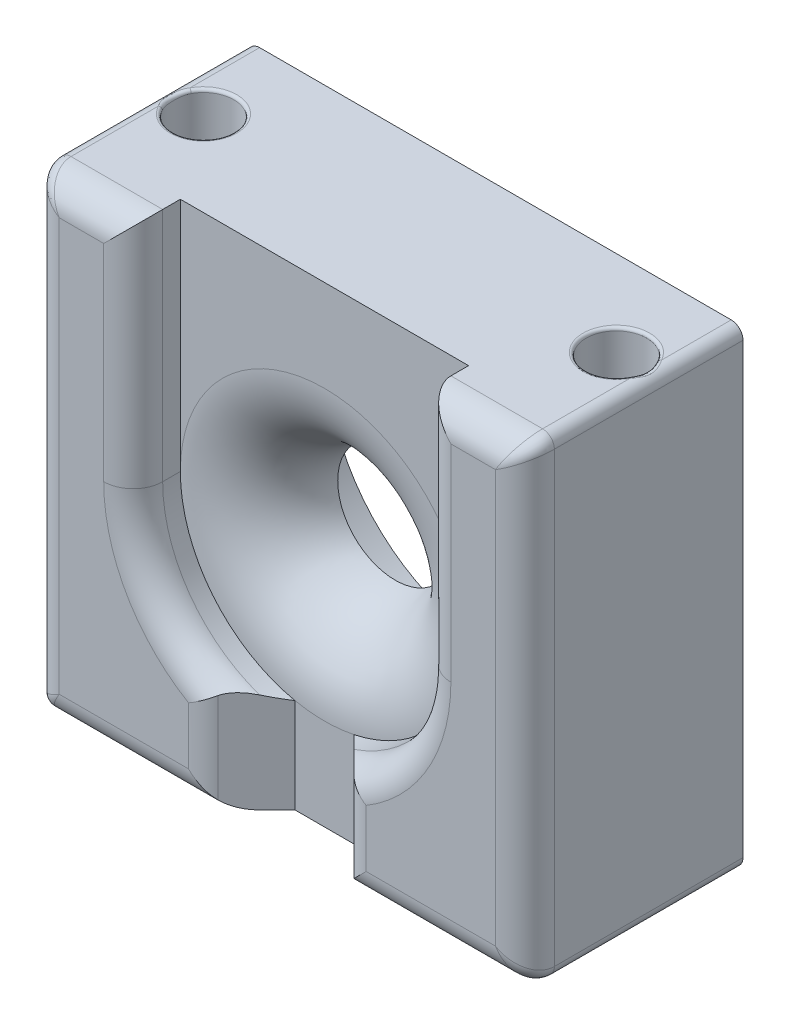
SolidWorks part; units mm, degrees
ref_plane "Front Plane" through (0, 0, 0) normal (1, 0, 0) x (0, 1, 0)
ref_plane "Top Plane" through (0, 0, 0) normal (0, 0, 1) x (0, 1, 0)
ref_plane "Right Plane" through (0, 0, 0) normal (0, 1, 0) x (-1, 0, 0)
sketch "Sketch1" plane through (0, 0, 0) normal (0, 0, 1) x (0, 1, 0)
  line L1 (-40, -42) -> (40, -42)
  line L2 (-40, -42) -> (-40, 42)
  line L3 (-40, 42) -> (40, 42)
  line L4 (40, -42) -> (40, 42)
  line L5 (-40, -42) -> (40, 42) construction
  line L6 (-40, 42) -> (40, -42) construction
  circle A0 centre (0, 0) radius 9.75
  point P0 (0, 0)
  dimension "D3" = 19.5
  dimension "D1" = 84
  dimension "D2" = 80
extrude "29 mm extrude" add sketch "Sketch1" along normal blind 29
sketch "Sketch2" plane through (0, 0, 0) normal (0, 0, -1) x (1, 0, 0)
  circle A0 centre (0, 0) radius 28.5
  dimension "D1" = 57
extrude "17 mm cut" cut sketch "Sketch2" against normal blind 17
fillet "25R funnel slope" radius 15 1 edges at (9.75, 0, 29)
sketch "Sketch3" plane through (0, 40, 0) normal (0, 1, 0) x (-1, 0, 0)
  line L0 (-42, 14.5) -> (42, 14.5) construction
  line L1 (-42, 29) -> (-42, 0) construction
  line L2 (42, 29) -> (42, 0) construction
  line L3 (0, 29) -> (0, 0) construction
  line L4 (-42, 29) -> (42, 29) construction
  line L5 (-42, 14.5) -> (-40.175, 14.5)
  circle A0 centre (-35.025, 14.5) radius 5.15
  circle A1 centre (35.025, 14.5) radius 5.15
  dimension "D1" = 10.3
extrude "10.2 mm" cut sketch "Sketch3" against normal blind 29.45 contours A0 | A1 region at (35.025, 40, 14.5) region at (-35.025, 40, 14.5)
sketch "Sketch5" plane through (0, 40, 0) normal (0, 1, 0) x (-1, 0, 0)
  circle A0 centre (-35.025, 14.5) radius 3.4
  circle A1 centre (-35.025, 14.5) radius 5.15 construction
  dimension "D1" = 6.8
extrude "6.8 mm bore" cut sketch "Sketch5" against normal through all
fillet "3R pig hole" radius 5 1 edges at (-28.5, 0, 17)
fillet "2R corners" radius 2 4 edges at (-42, 40, 14.5) (-42, -40, 14.5) (42, -40, 14.5) (42, 40, 14.5)
fillet "0.5R bolts" radius 0.5 4 edges at (-40.1603, 39.9936, 14.8885) (40.1603, 39.9936, 14.1115) (-29.875, 40, 14.5) (29.875, 40, 14.5)
mirror "Mirror1" about plane through (0, 0, 0) normal (1, 0, 0) of "6.8 mm bore"
sketch "Sketch6" plane through (0, 0, 29) normal (0, 0, 1) x (1, 0, 0)
  line L0 (-42, 38) -> (-42, -38) construction
  line L1 (-42, 0) -> (42, 0)
  line L2 (-42, 38) -> (-42, -38)
  line L3 (-40, -40) -> (40, -40)
  line L4 (42, 38) -> (42, -38)
  line L5 (-42, 0) -> (42, -40) construction
  line L6 (-42, -40) -> (42, 0) construction
  line L7 (42, -38) -> (42, 38) construction
  line L8 (-40, -40) -> (40, -40) construction
  line L9 (-39, -3) -> (-39, -37)
  line L10 (-39, -37) -> (39, -37)
  line L11 (39, -3) -> (39, -37)
  line L12 (-39, -3) -> (39, -3)
  line L13 (-42, -3) -> (42, -3)
  line L14 (-42, 0) -> (-42, -40) construction
  line L15 (-42, -40) -> (42, -40) construction
  line L16 (42, 0) -> (42, -40) construction
  line L17 (0, -37) -> (0, -40) construction
  line L18 (-3, 31.0296) -> (3, 37) construction
  line L19 (-3, -40) -> (3, -40)
  line L20 (-3, -40) -> (-3, -37)
  line L21 (-3, -37) -> (3, -37)
  line L22 (3, -40) -> (3, -37)
  line L23 (-3, -40) -> (3, -37) construction
  line L24 (-3, -37) -> (3, -40) construction
  line L25 (-3, -37) -> (3, -37)
  line L26 (-3, -37) -> (-3, -31.0296)
  line L28 (3, -37) -> (3, -31.0296)
  line L31 (-3, 37) -> (3, 31.0296) construction
  line L32 (-3, 37) -> (3, 40) construction
  line L33 (-3, 40) -> (3, 37) construction
  line L34 (0, 37) -> (0, 40) construction
  line L35 (-42, 40) -> (42, 0) construction
  line L36 (-42, 0) -> (42, 40) construction
  line L37 (3, 37) -> (3, 31.0296)
  line L38 (-3, 31.0296) -> (3, 31.0296)
  line L39 (-3, 37) -> (-3, 31.0296)
  line L40 (-3, 37) -> (3, 37)
  line L41 (3, 40) -> (3, 37)
  line L42 (-3, 37) -> (3, 37)
  line L43 (-3, 40) -> (-3, 37)
  line L44 (-3, 40) -> (3, 40)
  line L45 (-42, 3) -> (42, 3)
  line L46 (-39, 3) -> (39, 3)
  line L47 (39, 3) -> (39, 37)
  line L48 (-39, 37) -> (39, 37)
  line L49 (-39, 3) -> (-39, 37)
  line L50 (-40, 40) -> (40, 40)
  line L51 (-24.4469, 0) -> (-24.4469, 40)
  line L52 (24.4469, 0) -> (24.4469, 40)
  line L53 (-3, -31.0296) -> (-3, -21.4286)
  line L54 (-3, -21.4286) -> (3, -21.4286)
  line L55 (3, -21.4286) -> (3, -31.0296)
  line L57 (-3, -34.0148) -> (-3, -31.0296)
  arc A0 (40, 40) -> (42, 38) centre (40, 38) cw
  arc A1 (-42, -38) -> (-40, -40) centre (-40, -38) ccw
  arc A2 (40, -40) -> (42, -38) centre (40, -38) ccw
  arc A3 (3, -31.0296) -> (-3, -31.0296) centre (0, 0) ccw
  arc A4 (-42, 38) -> (-40, 40) centre (-40, 38) cw
  circle A5 centre (0, 0) radius 24.4469 construction
  point P4 (0, -20)
  point P19 (0, -38.5)
  point P36 (0, -34.0148)
  point P55 (0, 34.0148)
  point P56 (0, 38.5)
  point P61 (0, 20)
  circle M11 centre (0, 0) radius 24.4469
  line M12 (40, 40) -> (-40, 40)
  arc M13 (-40, 40) -> (-42, 38) centre (-40, 38) ccw
  line M14 (-42, 38) -> (-42, -38)
  arc M15 (-42, -38) -> (-40, -40) centre (-40, -38) ccw
  line M16 (-40, -40) -> (40, -40)
  arc M17 (40, -40) -> (42, -38) centre (40, -38) ccw
  line M18 (42, -38) -> (42, 38)
  arc M19 (42, 38) -> (40, 40) centre (40, 38) ccw
  dimension "D2" = 2
  dimension "D1" = 3
  dimension "D3" = 6
extrude "8 mm extrude" add sketch "Sketch6" along normal blind 8 contours L22 L13 L11 L10 M16 M17 M18 | L28 L10 L11 L12 M11 | L10 L26 L12 L9 M11 | L48 L51 L50 L45 L49 M13 M14 | L45 L51 L48 L49 | L52 L48 L47 L45 L4 M19 M12 | L52 L46 L47 L48 | L52 L1 L45 L46 M18 | L12 L13 L4 L1 M11 | L1 L51 L45 L2 | L13 L12 L1 M14 M11 | L20 L10 L9 L13 L2 M16 M15 | L55 A3 L12 M11 | L13 A3 L53 M11 | L46 A3 L52 | L51 A3 L46 | L46 A3 L1 L51 | L1 A3 L13 M11 | L1 A3 L46 L52 | L12 A3 L1 M11 region at (-27.7557, -1.5015, 29) region at (-27.7867, 1.4946, 29) region at (27.7867, 1.4946, 29) region at (27.7557, -1.5015, 29) region at (-36.563, -1.5033, 29) region at (-36.563, 1.5033, 29) region at (-26.9832, 9.083, 29) region at (-18.2958, -18.2958, 29) region at (36.563, 1.5033, 29) region at (36.563, -1.5033, 29) region at (26.9832, 9.083, 29) region at (18.2958, -18.2958, 29) region at (-32.4888, 21.7625, 29) region at (-26.9155, -24.9984, 29) region at (26.9155, -24.9984, 29) region at (32.4888, 21.7625, 29) region at (-41.5905, 20.5, 29) region at (-40.5, -3.5376, 29) region at (40.5, 3.4095, 29) region at (41.4624, -20.5, 29)
chamfer "Chamfer1" distance 10 angle 45 2 edges at (-3, -32.1311, 37) (3, -32.1311, 37)
fillet "Fillet1" radius 5 16 edges at (-41.4142, -39.4142, 37) (-42, 0, 37) (-41.4142, 39.4142, 37) (-32.2235, 40, 37) (-24.4469, 20, 37) (-21.3947, -11.8288, 37) (-13, -30.352, 37) (-26.5, -40, 37) (24.4469, 20, 37) (32.2235, 40, 37) (41.4142, 39.4142, 37) (42, 0, 37) (41.4142, -39.4142, 37) (26.5, -40, 37) (13, -30.352, 37) (21.3947, -11.8288, 37)
